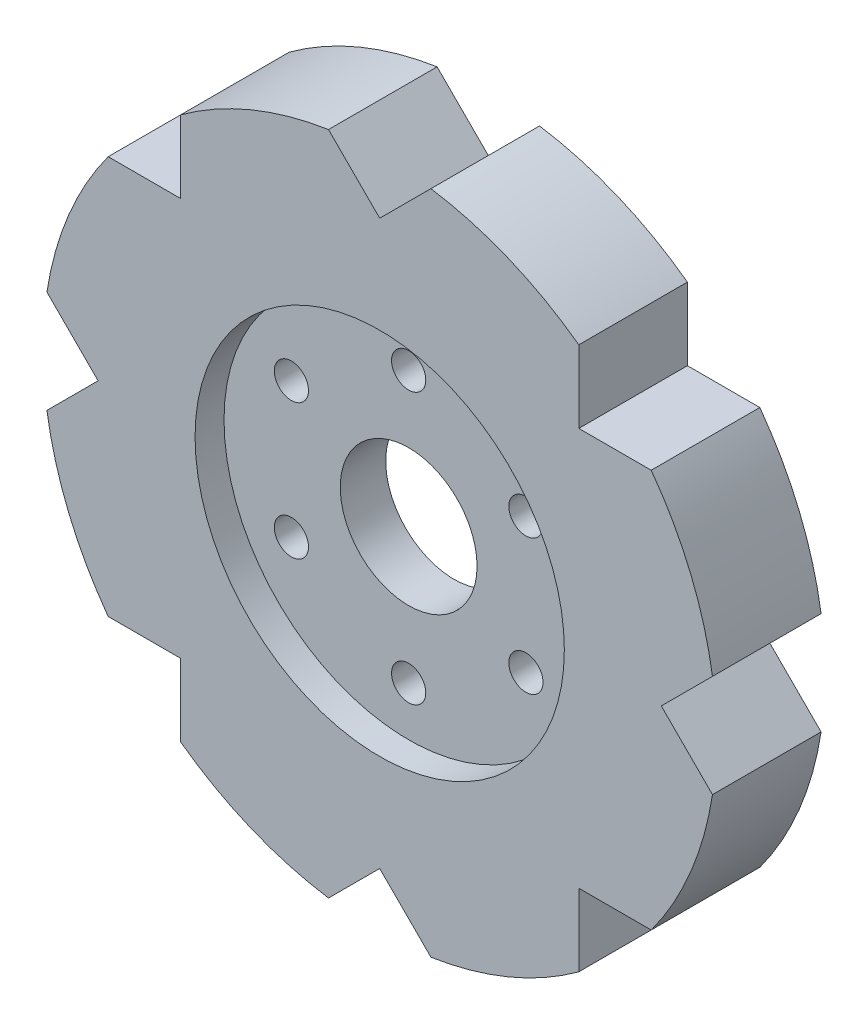
SolidWorks part; units mm, degrees
material "PE High Density Film"
ref_plane "Front Plane" through (0, 0, 0) normal (0, 0, 1) x (1, 0, 0)
ref_plane "Top Plane" through (0, 0, 0) normal (0, 1, 0) x (1, 0, 0)
ref_plane "Right Plane" through (0, 0, 0) normal (1, 0, 0) x (0, 0, -1)
sketch "Sketch1" plane through (0, 0, 0) normal (0, 0, 1) x (1, 0, 0)
  line L0 (0, 0) -> (0, 59.055) construction
  line L1 (-8.9803, 58.3682) -> (0, 49.388)
  line L2 (0, 49.388) -> (8.9803, 58.3682)
  line L3 (34.9226, 47.6226) -> (34.9226, 34.9226)
  line L4 (34.9226, 34.9226) -> (47.6226, 34.9226)
  line L5 (58.3682, 8.9803) -> (49.388, 0)
  line L6 (49.388, 0) -> (58.3682, -8.9803)
  line L7 (47.6226, -34.9226) -> (34.9226, -34.9226)
  line L8 (34.9226, -34.9226) -> (34.9226, -47.6226)
  line L9 (8.9803, -58.3682) -> (0, -49.388)
  line L10 (0, -49.388) -> (-8.9803, -58.3682)
  line L11 (-34.9226, -47.6226) -> (-34.9226, -34.9226)
  line L12 (-34.9226, -34.9226) -> (-47.6226, -34.9226)
  line L13 (-58.3682, -8.9803) -> (-49.388, 0)
  line L14 (-49.388, 0) -> (-58.3682, 8.9803)
  line L15 (-47.6226, 34.9226) -> (-34.9226, 34.9226)
  line L16 (-34.9226, 34.9226) -> (-34.9226, 47.6226)
  arc A0 (-58.3682, -8.9803) -> (-47.6226, -34.9226) centre (0, 0) ccw
  arc A1 (-47.6226, 34.9226) -> (-58.3682, 8.9803) centre (0, 0) ccw
  arc A2 (-34.9226, -47.6226) -> (-8.9803, -58.3682) centre (0, 0) ccw
  arc A3 (8.9803, -58.3682) -> (34.9226, -47.6226) centre (0, 0) ccw
  arc A4 (47.6226, -34.9226) -> (58.3682, -8.9803) centre (0, 0) ccw
  arc A5 (58.3682, 8.9803) -> (47.6226, 34.9226) centre (0, 0) ccw
  arc A6 (34.9226, 47.6226) -> (8.9803, 58.3682) centre (0, 0) ccw
  arc A7 (-8.9803, 58.3682) -> (-34.9226, 47.6226) centre (0, 0) ccw
  point P30 (0, 0)
  dimension "D1" = 118.11
  dimension "D2" = 45
  dimension "D3" = 12.7
  dimension "D4" = 8
extrude "Boss-Extrude1" add sketch "Sketch1" along normal blind 19.05
sketch "Sketch2" plane through (0, 0, 19.05) normal (0, 0, 1) x (1, 0, 0)
  circle A0 centre (0, 0) radius 12
  dimension "D1" = 24
extrude "Cut-Extrude1" cut sketch "Sketch2" against normal through all contours A0 region at (0, 0, 19.05)
sketch "Sketch3" plane through (0, 0, 19.05) normal (0, 0, 1) x (1, 0, 0)
  circle A0 centre (0, 0) radius 32.385
  dimension "D1" = 64.77
extrude "Cut-Extrude2" cut sketch "Sketch3" against normal blind 5.08
sketch "Sketch4" plane through (0, 0, 0) normal (0, 0, -1) x (-1, 0, 0)
  circle A0 centre (0, 0) radius 28.4
  dimension "D1" = 56.8
extrude "Cut-Extrude3" cut sketch "Sketch4" against normal blind 6
sketch "Sketch5" plane through (0, 0, 6) normal (0, 0, -1) x (-1, 0, 0)
  line L0 (0, 0) -> (0, 23.75) construction
  circle A0 centre (0, 0) radius 23.75 construction
  circle A1 centre (0, 23.75) radius 2.6
  circle A2 centre (20.5681, 11.875) radius 2.6
  circle A3 centre (20.5681, -11.875) radius 2.6
  circle A4 centre (0, -23.75) radius 2.6
  circle A5 centre (-20.5681, -11.875) radius 2.6
  circle A6 centre (-20.5681, 11.875) radius 2.6
  point P17 (0, 0)
  dimension "D1" = 47.5
  dimension "D2" = 5.2
  dimension "D3" = 6
hole_wizard "Ø6.0mm Dowel Hole1" positions "Sketch6" profile "Sketch8" hole size "Ø6.0" standard "ANSI Metric" end condition through all
sketch "Sketch6" plane through (0, 0, 6) normal (0, 0, -1) x (-1, 0, 0)
  point P0 (0, 23.75)
  point P3 (20.5681, 11.875)
  point P6 (20.5681, -11.875)
  point P9 (0, -23.75)
  point P13 (-20.5681, 11.875)
  point P16 (-20.5681, -11.875)
sketch "Sketch8" plane through (0, 23.75, 6) normal (1, 0, 0) x (0, 1, 0)
  line L0 (0, 0) -> (0, 13.05)
  line L1 (0, 13.05) -> (3, 13.05)
  line L2 (3, 13.05) -> (3, 0)
  line L5 (3, 0) -> (0, 0)
  line L11 (0, -6.35) -> (0, 107.95) construction
  dimension "Thru Hole Dia." = 6
  dimension "Thru Hole Depth" = 13.05
